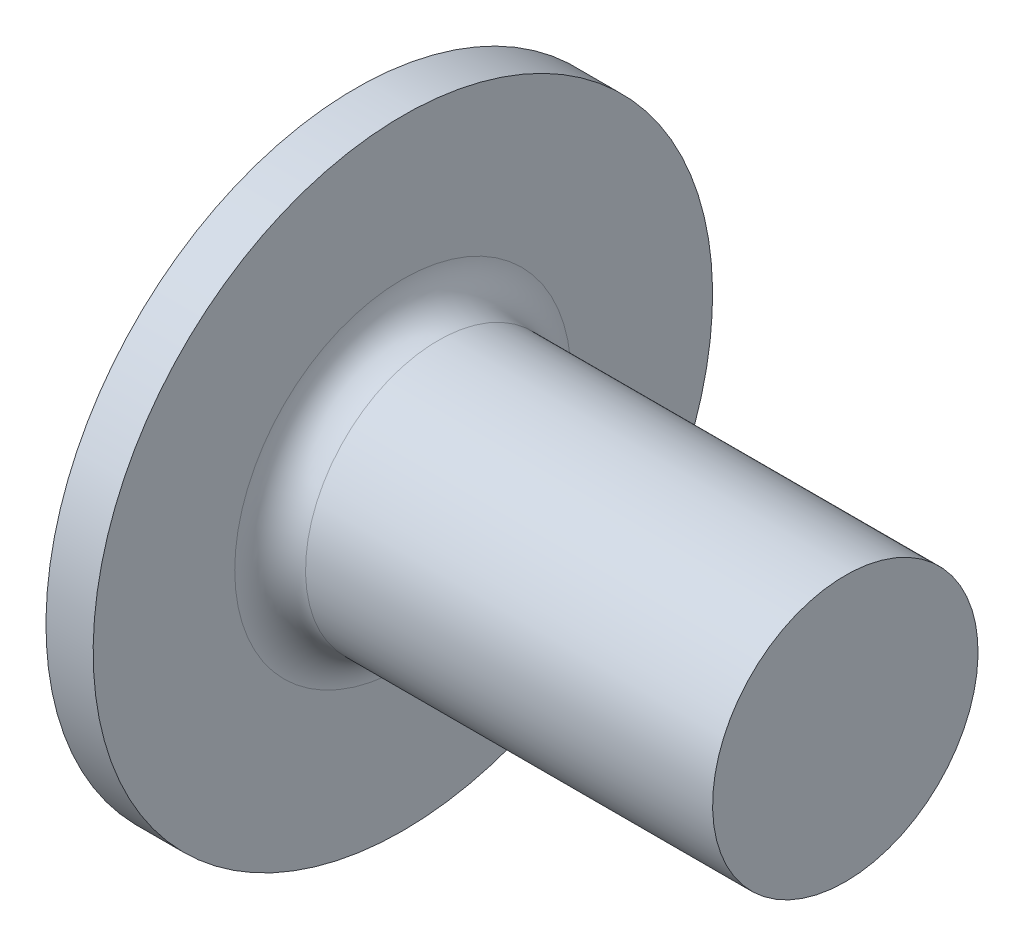
SolidWorks part; units mm, degrees
material "AISI 304"
ref_plane "Front Plane" through (0, 0, 0) normal (0, 0, 1) x (1, 0, 0)
ref_plane "Top Plane" through (0, 0, 0) normal (0, 1, 0) x (1, 0, 0)
ref_plane "Right Plane" through (0, 0, 0) normal (1, 0, 0) x (0, 0, -1)
ref_plane "Plane1" through (-0.8, 0, 0) normal (1, 0, 0) x (0, 0, -1)
sketch "Sketch1" plane through (0, 0, 0) normal (0, 0, 1) x (1, 0, 0)
  line L0 (-0.8, 0) -> (5, 0) construction
  line L1 (0, 1.5) -> (5, 1.5)
  line L2 (5, 1.5) -> (5, 0)
  line L3 (5, 0) -> (-0.8, 0)
  line L4 (-0.8, 0) -> (-0.8, 3.0381)
  line L5 (-0.8, 3.0381) -> (-0.5333, 3.5)
  line L6 (-0.5333, 3.5) -> (0, 3.5)
  line L7 (0, 3.5) -> (0, 1.5)
  dimension "M" = 3
  dimension "L" = 5
  dimension "FIX_1" = 30
  dimension "A" = 7
  dimension "E" = 0.8
  dimension "KSS_1" = 0.5333
revolve "Revolve1" add sketch "Sketch1" angle 360 about L0
cosmetic thread "Thread1" parameters "ATD"=2.459
chamfer "Chamfer1" [suppressed] distance 0.2 angle 45
sketch "Sketch2" plane through (-0.8, 0, 0) normal (1, 0, 0) x (0, 0, -1)
  line L0 (0, 0.875) -> (0, -0.875) construction
  line L1 (0.875, 0) -> (-0.875, 0) construction
  line L2 (0.7578, 0.4375) -> (-0.7578, -0.4375) construction
  line L3 (-0.7578, 0.4375) -> (0.7578, -0.4375) construction
  line L4 (0.4375, 0.7578) -> (-0.4375, -0.7578) construction
  line L5 (-0.4375, 0.7578) -> (0.4375, -0.7578) construction
  circle A0 centre (0, 0) radius 0.875 construction
  circle A1 centre (0, 0) radius 0.635 construction
  arc A2 (0.1693, 0.7443) -> (-0.1693, 0.7443) centre (0, 0.7) ccw
  arc A3 (0.7292, 0.2255) -> (0.5599, 0.5188) centre (0.6062, 0.35) ccw
  arc A4 (0.5599, -0.5188) -> (0.7292, -0.2255) centre (0.6062, -0.35) ccw
  arc A5 (-0.1693, -0.7443) -> (0.1693, -0.7443) centre (0, -0.7) ccw
  arc A6 (-0.7292, -0.2255) -> (-0.5599, -0.5188) centre (-0.6062, -0.35) ccw
  arc A7 (-0.5599, 0.5188) -> (-0.7292, 0.2255) centre (-0.6062, 0.35) ccw
  arc A8 (0.1693, 0.7443) -> (0.5599, 0.5188) centre (0.476, 0.8245) ccw
  arc A9 (0.7292, 0.2255) -> (0.7292, -0.2255) centre (0.952, 0) ccw
  arc A10 (0.5599, -0.5188) -> (0.1693, -0.7443) centre (0.476, -0.8245) ccw
  arc A11 (-0.1693, -0.7443) -> (-0.5599, -0.5188) centre (-0.476, -0.8245) ccw
  arc A12 (-0.7292, -0.2255) -> (-0.7292, 0.2255) centre (-0.952, 0) ccw
  arc A13 (-0.5599, 0.5188) -> (-0.1693, 0.7443) centre (-0.476, 0.8245) ccw
  dimension "MSM_1" = 1.75
  dimension "MSM_2" = 1.27
  dimension "MSM_3" = 0.175
  dimension "FIX_5" = 30
  dimension "FIX_6" = 30
  dimension "FIX_7" = 60
  dimension "FIX_8" = 60
extrude "Cut-Extrude1" cut sketch "Sketch2" along normal blind 0.75
fillet "Fillet1" radius 0.4 1 edges at (0, -1.5, 0)
equation "\"KSS_1@Sketch1\"= \"E@Sketch1\" * 2 / 3"
